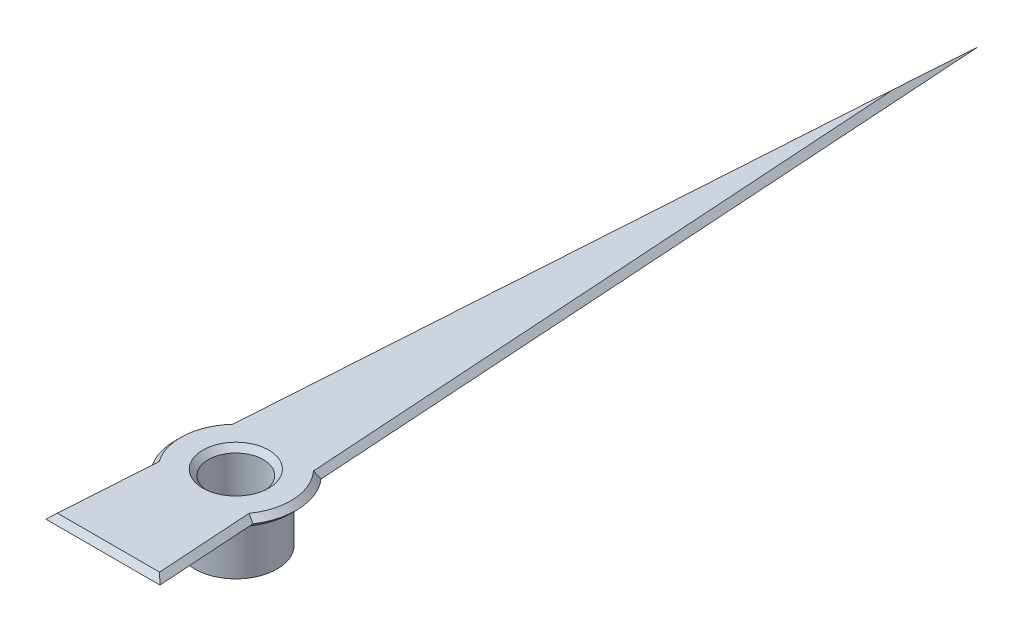
SolidWorks part; units mm, degrees
ref_plane "Front Plane" through (0, 0, 0) normal (0, 0, 1) x (1, 0, 0)
ref_plane "Top Plane" through (0, 0, 0) normal (0, 1, 0) x (1, 0, 0)
ref_plane "Right Plane" through (0, 0, 0) normal (1, 0, 0) x (0, 0, -1)
sketch "Sketch2" plane through (0, 0, 0) normal (0, 1, 0) x (1, 0, 0)
  circle A0 centre (0, 0) radius 0.75
  dimension "D1" = 1.5
extrude "Boss-Extrude1" add sketch "Sketch2" against normal blind 1
sketch "Sketch3" plane through (0, 0, 0) normal (0, 1, 0) x (1, 0, 0)
  circle A0 centre (0, 0) radius 1.1
  dimension "D1" = 2.2
extrude "Boss-Extrude2" add sketch "Sketch3" along normal blind 0.2
sketch "Sketch4" plane through (0, 0.2, 0) normal (0, 1, 0) x (1, 0, 0)
  line L1 (0, 13.5) -> (-1.0363, -2.4166)
  line L2 (-1.0363, -2.4166) -> (1.0363, -2.4166)
  line L3 (0, 13.5) -> (1.0363, -2.4166)
  point P6 (0, -2.4166)
extrude "Boss-Extrude3" add sketch "Sketch4" against normal blind 0.2
sketch "Sketch5" plane through (0, 0.2, 0) normal (0, 1, 0) x (1, 0, 0)
  circle A0 centre (0, 0) radius 0.5
  dimension "D1" = 1
extrude "Cut-Extrude1" cut sketch "Sketch5" against normal blind 1
chamfer "Chamfer1" distance 0.1 angle 45 16 edges at (0, 0, 0.75) (-0.9773, 0, 1.511) (0, 0, 2.4166) (0.9773, 0, 1.511) (1.0977, 0, -0.0715) (0.4161, 0, -7.1097) (-0.4161, 0, -7.1097) (-1.0977, 0, -0.0715) (-0.4161, 0.2, -7.1097) (0.4161, 0.2, -7.1097) (1.0977, 0.2, -0.0715) (0.9773, 0.2, 1.511) (0, 0.2, 2.4166) (-0.9773, 0.2, 1.511) (-1.0977, 0.2, -0.0715) (0, 0.2, 0.5)
